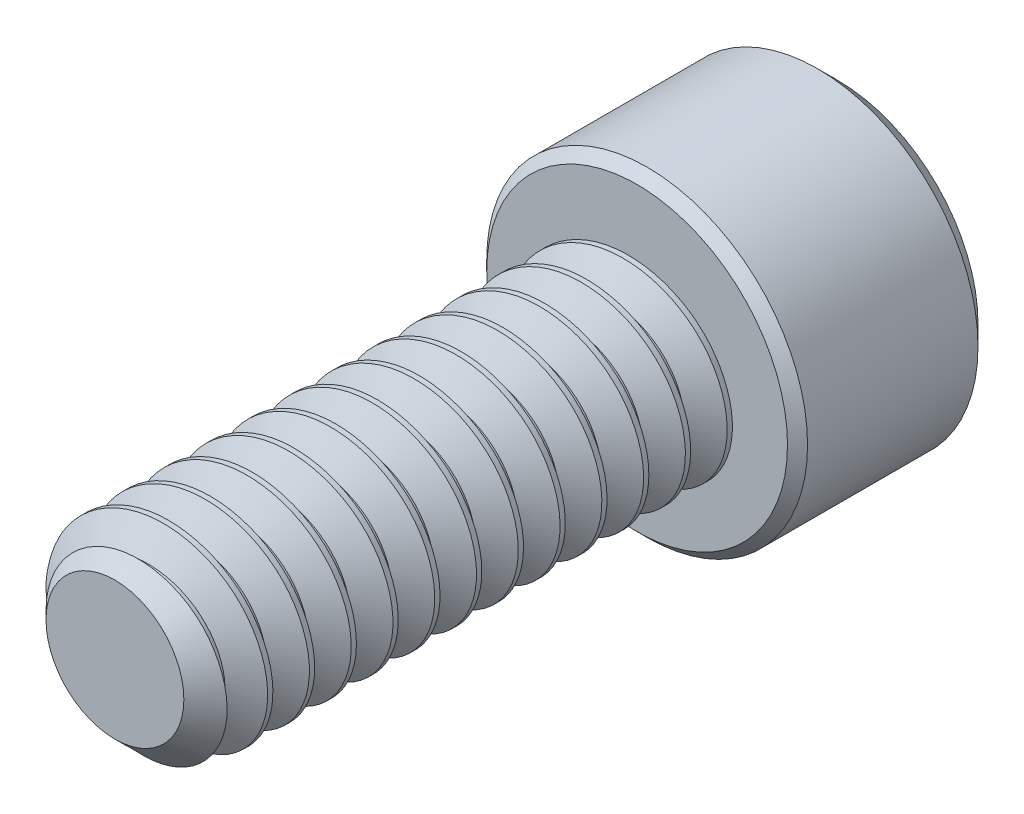
SolidWorks part; units mm, degrees
ref_plane "Front Plane" through (0, 0, 0) normal (0, 0, 1) x (1, 0, 0)
ref_plane "Top Plane" through (0, 0, 0) normal (0, 1, 0) x (1, 0, 0)
ref_plane "Right Plane" through (0, 0, 0) normal (1, 0, 0) x (0, 0, -1)
sketch "Sketch1" plane through (0, 0, 0) normal (0, 0, 1) x (1, 0, 0)
  line L0 (0, 0.762) -> (0, -0.762) construction
  circle A0 centre (0, 0) radius 0.762
  dimension "OD" = 1.524
extrude "Extrude1" add sketch "Sketch1" against normal blind 3.9688
sketch "Sketch2" plane through (0, 0, 0) normal (0, 0, 1) x (1, 0, 0)
  circle A0 centre (0, 0) radius 0.762 construction
  circle A1 centre (0, 0) radius 0.762
curve "Helix/Spiral1" pitch 0.3175 height 4.2862 radius 0.762 centre (0, 0, 0) axis (0, 0, -1) start towards (0, 1, 0) parameters "pitch"=0.3175
chamfer "Chamfer3" distance 0.2381 angle 45 1 edges at (0.762, 0, 0)
sketch "Sketch3" plane through (0, 0, 0) normal (1, 0, 0) x (0, 0, -1)
  line L0 (-0.2778, 0.762) -> (-0.1588, 0.5558)
  line L1 (-0.1588, 0.5558) -> (-0.1191, 0.5558)
  line L2 (-0.1191, 0.5558) -> (0, 0.762)
  line L3 (-0.2778, 0.762) -> (0, 0.762)
  line L4 (-0.1389, 0.762) -> (-0.1389, 0.5558) construction
  line L5 (-0.2183, 0.6589) -> (-0.0595, 0.6589) construction
  line L6 (0, 0.762) -> (0, -0.762) construction
  dimension "D1" = 0.0397
  dimension "D2" = 0.1588
  dimension "D3" = 60
sweep "Cut-Sweep1" cut profiles "Sketch3" path "Helix/Spiral1" align with end faces yes
sketch "Sketch6" plane through (0, 0, -3.9688) normal (0, 0, -1) x (-1, 0, 0)
  circle A0 centre (0, 0) radius 1.2192
  dimension "head dia" = 2.4384
extrude "Extrude2" add sketch "Sketch6" along normal blind 1.524
sketch "Sketch7" plane through (0, 0, -5.4928) normal (0, 0, -1) x (-1, 0, 0)
  line L1 (0, 0.7332) -> (-0.635, 0.3666)
  line L2 (-0.635, 0.3666) -> (-0.635, -0.3666)
  line L3 (-0.635, -0.3666) -> (0, -0.7332)
  line L4 (0, -0.7332) -> (0.635, -0.3666)
  line L5 (0.635, -0.3666) -> (0.635, 0.3666)
  line L6 (0.635, 0.3666) -> (0, 0.7332)
  circle A0 centre (0, 0) radius 0.635 construction
  dimension "hex dia" = 1.27
extrude "Cut-Extrude1" cut sketch "Sketch7" against normal blind 0.9525
sketch "Sketch8" plane through (0, 0, -5.4928) normal (0, 0, -1) x (-1, 0, 0)
  circle A0 centre (0, 0) radius 0.7332
extrude "Cut-Extrude2" cut sketch "Sketch8" against normal blind 0.1524 draft 45
chamfer "Chamfer1" distance 0.1524 angle 45 1 edges at (-1.2192, 0, -5.4928)
chamfer "Chamfer2" distance 0.0762 angle 45 1 edges at (-1.2192, 0, -3.9688)
sketch "Sketch9" plane through (0, 0, 0) normal (1, 0, 0) x (0, 0, -1)
  line L0 (0, 0.762) -> (0, -0.762) construction
  line L1 (1.7463, 0.762) -> (1.7463, -0.762) construction
  line L2 (3.9688, 1.2192) -> (3.9688, -1.2192) construction
  line L3 (5.4927, 1.2192) -> (5.4927, -1.2192) construction
  line L4 (5.4928, 0) -> (0, 0) construction
  dimension "D1" = 1.7463
  dimension "D2" = 1.524
  dimension "D3" = 2.4384
  dimension "D4" = 3.9688
equation "\"D3@Helix/Spiral1\" = \"screw length@Extrude1\"+\"pitch@Helix/Spiral1\""
equation "\"D1@Sketch3\" = \"pitch@Helix/Spiral1\"*.125"
equation "\"D2@Sketch3\" = \"pitch@Helix/Spiral1\"*.5"
equation "\"D1@Cut-Extrude1\" = \"hex dia@Sketch7\"*.75"
equation "\"D1@Chamfer1\" = \"head depth@Extrude2\"/10"
equation "\"D1@Sketch9\" = \"pitch@Helix/Spiral1\"*5.5"
equation "\"D1@Chamfer2\" = \"D1@Chamfer1\"/2"
equation "\"D1@Cut-Extrude2\" = \"D1@Chamfer2\"*2"
equation "\"D1@Chamfer3\" = \"pitch@Helix/Spiral1\"*.750"
equation "\"D2@Sketch9\" = \"head depth@Extrude2\""
equation "\"D3@Sketch9\" = \"head dia@Sketch6\""
equation "\"D4@Sketch9\" = \"screw length@Extrude1\""
